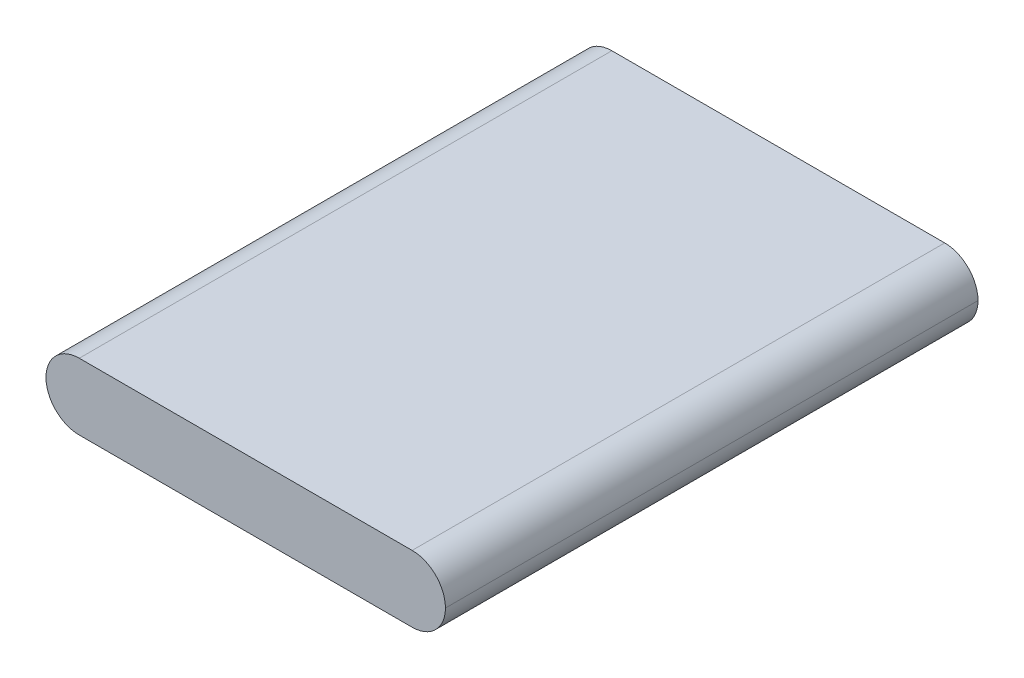
SolidWorks part; units mm, degrees
ref_plane "Front Plane" through (0, 0, 0) normal (0, 0, 1) x (1, 0, 0)
ref_plane "Top Plane" through (0, 0, 0) normal (0, 1, 0) x (1, 0, 0)
ref_plane "Right Plane" through (0, 0, 0) normal (1, 0, 0) x (0, 0, -1)
sketch "Sketch1" plane through (0, 0, 0) normal (0, 1, 0) x (1, 0, 0)
  line L1 (-15, -20) -> (15, -20)
  line L2 (-15, -20) -> (-15, 20)
  line L3 (-15, 20) -> (15, 20)
  line L4 (15, -20) -> (15, 20)
  line L5 (-15, -20) -> (15, 20) construction
  line L6 (-15, 20) -> (15, -20) construction
  point P0 (0, 0)
  dimension "D1" = 30
  dimension "D2" = 40
extrude "Extrude1" add sketch "Sketch1" along normal mid plane 5
fillet "Fillet1" radius 2.5 4 edges at (15, -2.5, 0) (15, 2.5, 0) (-15, -2.5, 0) (-15, 2.5, 0)
